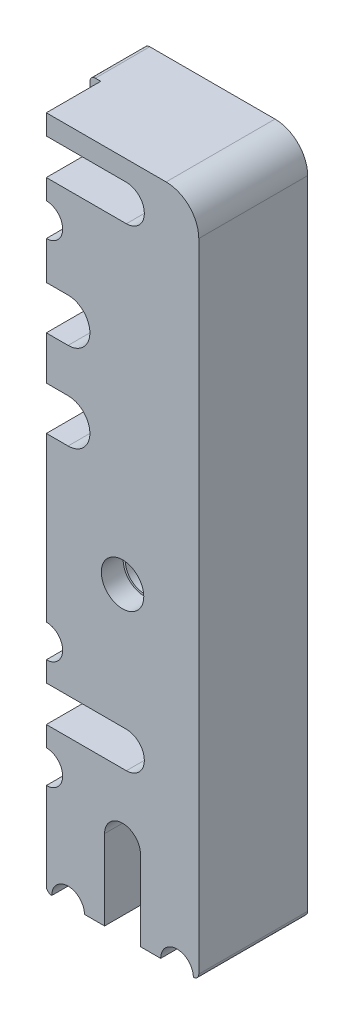
SolidWorks part; units mm, degrees
ref_plane "Front Plane" through (0, 0, 0) normal (0, 0, 1) x (1, 0, 0)
ref_plane "Top Plane" through (0, 0, 0) normal (0, 1, 0) x (1, 0, 0)
ref_plane "Right Plane" through (0, 0, 0) normal (1, 0, 0) x (0, 0, -1)
sketch "Sketch4" plane through (0, 0, 0) normal (1, 0, 0) x (0, 0, -1)
  line L0 (10, 62) -> (0, 62)
  line L1 (0, 0) -> (10, 0)
  line L2 (0, 0) -> (0, 62)
  line L8 (10, 0) -> (10, 62)
  point P6 (5, 0)
  dimension "D1" = 10
  dimension "D2" = 62
extrude "Boss-Extrude1" add sketch "Sketch4" along normal blind 14
sketch "Sketch10" plane through (0, 0, -10) normal (0, 0, -1) x (-1, 0, 0)
  line L0 (0, 0) -> (0, 62) construction
  line L1 (0, 11.5) -> (1, 11.5)
  line L2 (0, 11.5) -> (0, 18.5)
  line L3 (0, 18.5) -> (1, 18.5)
  line L4 (1, 11.5) -> (1, 18.5)
  line L6 (0, 55) -> (1, 55)
  line L7 (0, 55) -> (0, 62)
  line L8 (0, 62) -> (1, 62)
  line L9 (1, 55) -> (1, 62)
  line L11 (-14, 62) -> (0, 62) construction
  line L12 (0, 0) -> (0, 62) construction
  line L13 (1, 15) -> (-4.0508, 15) construction
  line L14 (-14, 0) -> (0, 0) construction
  line L15 (-14, 0) -> (0, 0) construction
  line L16 (-3.5, 0) -> (-10.5, 0)
  line L17 (-3.5, 0) -> (-3.5, -1)
  line L18 (-3.5, -1) -> (-10.5, -1)
  line L19 (-10.5, 0) -> (-10.5, -1)
  line L20 (-7, -1) -> (-7, -0.3035) construction
  dimension "D1" = 7
  dimension "D2" = 1
  dimension "D3" = 15
  dimension "D4" = 7
  dimension "D5" = 7
  dimension "D6" = 1
  dimension "D7" = 7
extrude "Boss-Extrude2" add sketch "Sketch10" against normal blind 5
sketch "Sketch5" plane through (0, 0, 0) normal (0, 0, 1) x (1, 0, 0)
  line L0 (2, 44.5) -> (0, 44.5)
  line L1 (14, 0) -> (0, 0) construction
  line L2 (0, 62) -> (0, 0) construction
  line L3 (0, 44.5) -> (0, 48.5)
  line L4 (0, 48.5) -> (2, 48.5)
  line L5 (2, 36.5) -> (0, 36.5)
  line L6 (0, 36.5) -> (0, 40.5)
  line L7 (0, 40.5) -> (2, 40.5)
  arc A0 (2, 44.5) -> (2, 48.5) centre (2, 46.5) ccw
  arc A1 (2, 36.5) -> (2, 40.5) centre (2, 38.5) ccw
  dimension "D1" = 4
  dimension "D4" = 4
  dimension "D2" = 2
  dimension "D3" = 46.5
  dimension "D5" = 8
extrude "Cut-Extrude2" cut sketch "Sketch5" against normal through all
sketch "Sketch9" plane through (0, 0, 0) normal (0, 0, 1) x (1, 0, 0)
  line L6 (14, 0) -> (0, 0) construction
  line L12 (-1, 11.5) -> (-1, 18.5) construction
  line L16 (0, 53.5) -> (-1, 53.5) construction
  line L17 (0, 52) -> (-1, 52)
  line L18 (0, 55) -> (-1, 55)
  line L19 (0, 20) -> (-1, 20) construction
  line L20 (0, 36.5) -> (0, 0) construction
  line L21 (0, 18.5) -> (-1, 18.5)
  line L22 (0, 21.5) -> (-1, 21.5)
  line L23 (0, 10) -> (-1, 10) construction
  line L24 (0, 8.5) -> (-1, 8.5)
  line L25 (0, 11.5) -> (-1, 11.5)
  line L26 (2, -1) -> (2, 0) construction
  line L27 (0.5, -1) -> (0.5, 0)
  line L28 (3.5, -1) -> (3.5, 0)
  line L29 (12, 0) -> (12, -1) construction
  line L30 (13.5, 0) -> (13.5, -1)
  line L31 (10.5, 0) -> (10.5, -1)
  line L33 (0, 62) -> (0, 48.5) construction
  line L34 (-1, 55) -> (-1, 62) construction
  line L35 (0, 55) -> (-1, 55) construction
  line L36 (-1, 18.5) -> (0, 18.5) construction
  line L37 (0, 11.5) -> (-1, 11.5) construction
  line L38 (3.5, -1) -> (3.5, 0) construction
  line L39 (10.5, -1) -> (3.5, -1) construction
  line L40 (10.5, 0) -> (10.5, -1) construction
  arc A8 (0, 52) -> (0, 55) centre (0, 53.5) ccw
  arc A9 (-1, 55) -> (-1, 52) centre (-1, 53.5) ccw
  arc A10 (0, 18.5) -> (0, 21.5) centre (0, 20) ccw
  arc A11 (-1, 21.5) -> (-1, 18.5) centre (-1, 20) ccw
  arc A12 (0, 8.5) -> (0, 11.5) centre (0, 10) ccw
  arc A13 (-1, 11.5) -> (-1, 8.5) centre (-1, 10) ccw
  arc A14 (0.5, -1) -> (3.5, -1) centre (2, -1) ccw
  arc A15 (3.5, 0) -> (0.5, 0) centre (2, 0) ccw
  arc A16 (13.5, 0) -> (10.5, 0) centre (12, 0) ccw
  arc A17 (10.5, -1) -> (13.5, -1) centre (12, -1) ccw
  point P36 (-0.5, 53.5)
  point P43 (-0.5, 20)
  point P52 (-0.5, 10)
  point P59 (2, -0.5)
  point P66 (12, -0.5)
  dimension "D1" = 1.5
extrude "Cut-Extrude6" cut sketch "Sketch9" against normal through all
sketch "Sketch11" plane through (0, 0, 0) normal (0, 0, 1) x (1, 0, 0)
  line L0 (0, 36.5) -> (0, 21.5) construction
  line L1 (10.5, 0) -> (3.5, 0) construction
  circle A0 centre (7, 28) radius 1.75
  dimension "D3" = 3.5
  dimension "D1" = 7
  dimension "D2" = 28
extrude "Cut-Extrude7" cut sketch "Sketch11" against normal blind 8.5
sketch "Sketch12" plane through (0, 0, 0) normal (0, 0, 1) x (1, 0, 0)
  circle A0 centre (7, 28) radius 1.95
  dimension "D1" = 3.9
extrude "Cut-Extrude8" cut sketch "Sketch12" against normal blind 2
sketch "Sketch13" plane through (0, 0, 0) normal (0, 0, 1) x (1, 0, 0)
  line L0 (7, 7.35) -> (7, -1) construction
  line L1 (8.65, 7.35) -> (8.65, -1)
  line L2 (5.35, 7.35) -> (5.35, -1)
  line L3 (7.35, 15) -> (-1, 15) construction
  line L4 (7.35, 13.35) -> (-1, 13.35)
  line L5 (7.35, 16.65) -> (-1, 16.65)
  line L6 (7.35, 58.5) -> (-1, 58.5) construction
  line L7 (7.35, 56.85) -> (-1, 56.85)
  line L8 (7.35, 60.15) -> (-1, 60.15)
  line L9 (-1, 55) -> (-1, 62) construction
  line L10 (-1, 11.5) -> (-1, 18.5) construction
  line L11 (10.5, -1) -> (3.5, -1) construction
  arc A0 (8.65, 7.35) -> (5.35, 7.35) centre (7, 7.35) ccw
  arc A1 (5.35, -1) -> (8.65, -1) centre (7, -1) ccw
  arc A2 (7.35, 13.35) -> (7.35, 16.65) centre (7.35, 15) ccw
  arc A3 (-1, 16.65) -> (-1, 13.35) centre (-1, 15) ccw
  arc A4 (7.35, 56.85) -> (7.35, 60.15) centre (7.35, 58.5) ccw
  arc A5 (-1, 60.15) -> (-1, 56.85) centre (-1, 58.5) ccw
  point P2 (7, 3.175)
  point P7 (3.175, 15)
  point P14 (3.175, 58.5)
  dimension "D1" = 1.65
  dimension "D2" = 8.35
extrude "Cut-Extrude9" cut sketch "Sketch13" against normal blind 9
fillet "Fillet1" radius 3 1 edges at (14, 62, -5)
fillet "Fillet3" radius 0.5 14 edges at (14, 0, -5) (0, 0, -5) (-1, 55, -7.5) (-1, 62, -7.5) (-1, 18.5, -7.5) (-1, 11.5, -7.5) (3.5, -1, -7.5) (10.5, -1, -7.5) (-1, 56.85, -7) (-1, 60.15, -7) (-1, 13.35, -7) (-1, 16.65, -7) (5.35, -1, -7) (8.65, -1, -7)
